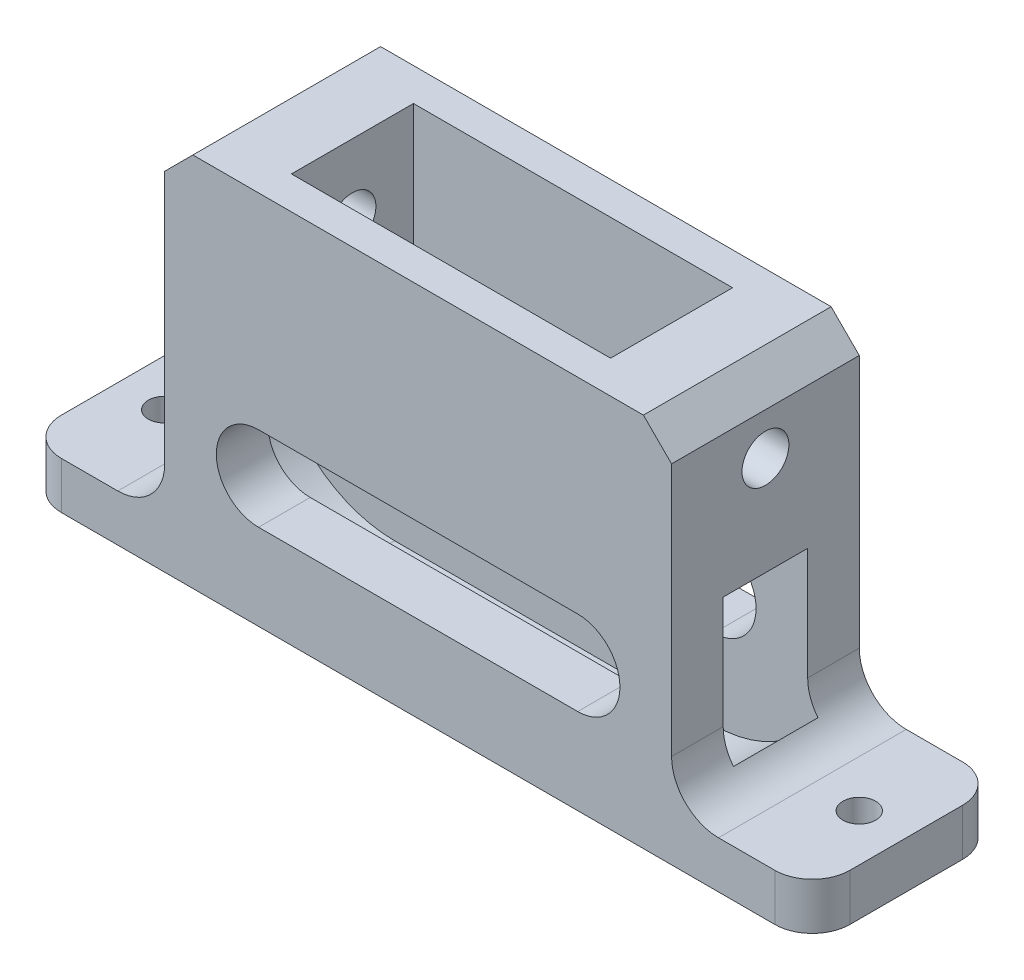
SolidWorks part; units mm, degrees
ref_plane "Front Plane" through (0, 0, 0) normal (0, 0, 1) x (1, 0, 0)
ref_plane "Top Plane" through (0, 0, 0) normal (0, 1, 0) x (1, 0, 0)
ref_plane "Right Plane" through (0, 0, 0) normal (1, 0, 0) x (0, 0, -1)
sketch "Sketch1" plane through (0, 0, 0) normal (0, 1, 0) x (1, 0, 0)
  line L1 (-27, 10) -> (27, 10)
  line L2 (-27, 10) -> (-27, -10)
  line L3 (-27, -10) -> (27, -10)
  line L4 (27, 10) -> (27, -10)
  line L5 (-27, 10) -> (27, -10) construction
  line L6 (-27, -10) -> (27, 10) construction
  point P0 (0, 0)
  dimension "D1" = 20
  dimension "D2" = 54
extrude "Boss-Extrude1" add sketch "Sketch1" along normal blind 40
sketch "Sketch4" plane through (0, 0, 0) normal (0, -1, 0) x (1, 0, 0)
  line L0 (27, -10) -> (-27, -10) construction
  line L1 (-27, 10) -> (-42, 10)
  line L2 (-27, 10) -> (-27, -10)
  line L3 (-27, -10) -> (-42, -10)
  line L4 (-42, 10) -> (-42, -10)
  line L5 (0, -11) -> (0, 11) construction
  line L6 (42, 10) -> (42, -10)
  line L7 (27, -10) -> (42, -10)
  line L8 (27, 10) -> (27, -10)
  line L9 (27, 10) -> (42, 10)
  dimension "D1" = 15
extrude "Boss-Extrude2" add sketch "Sketch4" against normal blind 5
fillet "Fillet1" radius 5 2 edges at (27, 5, 0) (-27, 5, 0)
sketch "Sketch6" plane through (0, 40, 0) normal (0, -1, 0) x (1, 0, 0)
  line L0 (17, 6.5) -> (-17, -6.5) construction
  line L1 (-17, 6.5) -> (17, 6.5)
  line L2 (-17, 6.5) -> (-17, -6.5)
  line L3 (-17, -6.5) -> (17, -6.5)
  line L4 (17, 6.5) -> (17, -6.5)
  line L5 (-27, -10) -> (-27, 10) construction
  dimension "D1" = 10
  dimension "D2" = 13
extrude "Cut-Extrude3" cut sketch "Sketch6" along normal offset from surface (26.35 mm away) 13.65 up to face at (0, 0, 0)
sketch "Sketch7" plane through (0, 0, 10) normal (0, 0, 1) x (1, 0, 0)
  line L0 (-17, 13.65) -> (17, 13.65) construction
  line L4 (-17, 18.15) -> (17, 18.15)
  line L8 (-17, 9.15) -> (17, 9.15)
  line L9 (0, 0) -> (0, 40) construction
  line L10 (-27, 40) -> (27, 40) construction
  line L11 (-17, 13.65) -> (-17, 40) construction
  line L12 (-42, 0) -> (42, 0) construction
  arc A2 (-17, 18.15) -> (-17, 9.15) centre (-17, 13.65) ccw
  arc A3 (17, 9.15) -> (17, 18.15) centre (17, 13.65) ccw
  point P2 (0, 13.65)
  dimension "D1" = 9
  dimension "D2" = 13.65
extrude "Cut-Extrude4" cut sketch "Sketch7" against normal through all
sketch "Sketch3" plane through (-27, 0, 0) normal (-1, 0, 0) x (0, 0, 1)
  line L2 (-10, 32.52) -> (10, 32.52) construction
  line L3 (-10, 40) -> (-10, 10) construction
  line L4 (10, 40) -> (10, 10) construction
  line L6 (10, 0) -> (-10, 0) construction
  line L7 (-10, 40) -> (-10, 10) construction
  line L8 (-10, 13.65) -> (-10, 32.52) construction
  circle A0 centre (0, 32.52) radius 2.5
  dimension "D1" = 5
  dimension "D2" = 13.65
  dimension "D3" = 18.87
extrude "Cut-Extrude2" cut sketch "Sketch3" against normal through all
ref_plane "Plane2" through (0, 0, -4.5) normal (0, 0, -1) x (-1, 0, 0)
sketch "Sketch8" plane through (0, 0, -4.5) normal (0, 0, -1) x (-1, 0, 0)
  line L0 (-17, 13.65) -> (17, 13.65) construction
  line L1 (-17, 26.65) -> (17, 26.65)
  line L2 (-17, 0.65) -> (17, 0.65)
  arc A1 (-17, 26.65) -> (-17, 0.65) centre (-17, 13.65) ccw
  arc A2 (17, 0.65) -> (17, 26.65) centre (17, 13.65) ccw
  point P3 (0, 13.65)
  dimension "D1" = 13
extrude "Cut-Extrude5" cut sketch "Sketch8" against normal blind 9
sketch "Sketch9" plane through (0, 5, 0) normal (0, 1, 0) x (1, 0, 0)
  line L0 (-32, 0) -> (-42, 0) construction
  line L1 (-32, -10) -> (-32, 10) construction
  line L2 (-42, -10) -> (-42, 10) construction
  line L3 (32, 0) -> (42, 0) construction
  line L4 (32, 10) -> (32, -10) construction
  line L5 (42, 10) -> (42, -10) construction
  circle A0 centre (-37, 0) radius 1.75
  circle A1 centre (37, 0) radius 1.75
  dimension "D1" = 3.5
  dimension "D2" = 3.5
extrude "Cut-Extrude6" cut sketch "Sketch9" against normal through all
fillet "Fillet2" radius 4 4 edges at (-42, 2.5, -10) (42, 2.5, 10) (42, 2.5, -10) (-42, 2.5, 10)
chamfer "Chamfer1" distance 3 angle 45 2 edges at (27, 40, 0) (-27, 40, 0)
